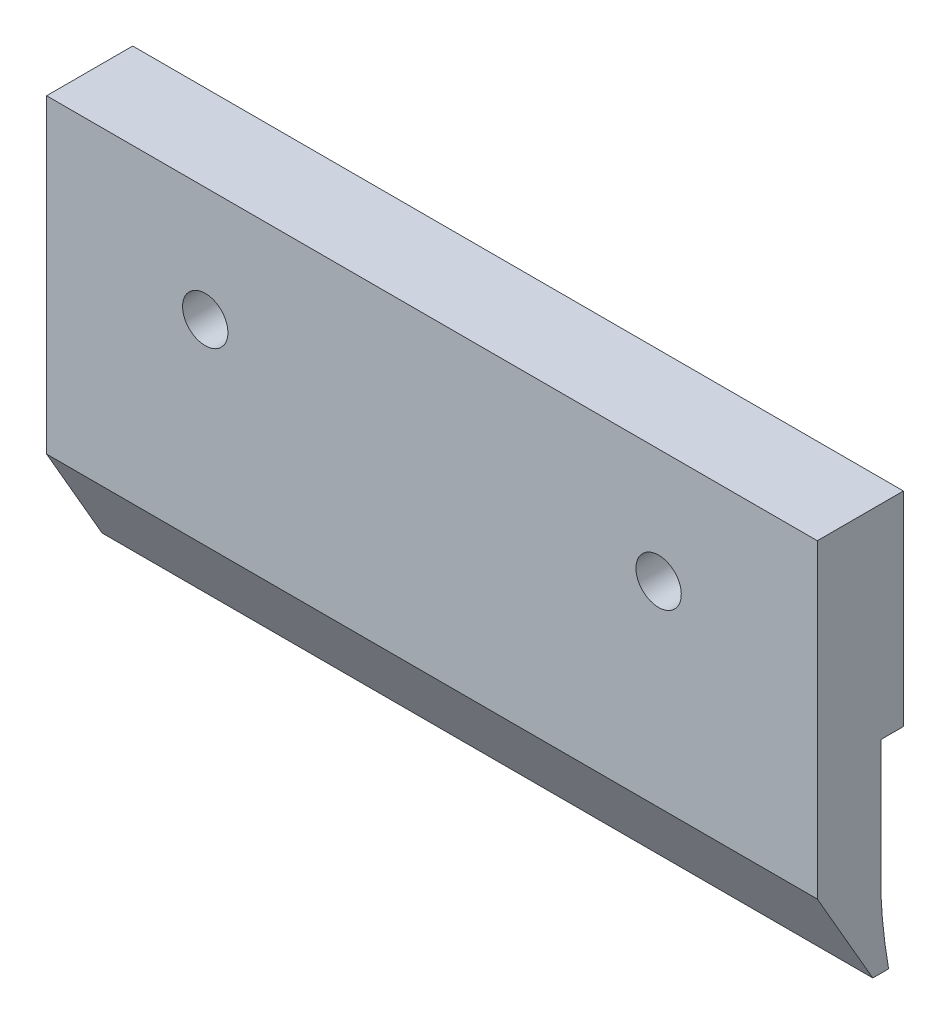
SolidWorks part; units mm, degrees
ref_plane "Front Plane" through (0, 0, 0) normal (0, 0, 1) x (1, 0, 0)
ref_plane "Top Plane" through (0, 0, 0) normal (0, 1, 0) x (1, 0, 0)
ref_plane "Right Plane" through (0, 0, 0) normal (1, 0, 0) x (0, 0, -1)
sketch "Sketch1" plane through (0, 0, 0) normal (1, 0, 0) x (0, 0, -1)
  line L0 (0, 0) -> (1, 0)
  line L1 (1, 0) -> (1, 9)
  line L2 (0, 0) -> (0, -5.7849)
  line L3 (0, 0) -> (0, -5.7849) construction
  line L4 (1, 9) -> (-2.8, 9)
  line L5 (-2.8, 9) -> (-2.8, 0)
  line L6 (-2.8, 0) -> (-2.8, -4.6892)
  line L10 (-0.3512, -8.9306) -> (-2.8, -4.6892)
  line L11 (-0.3512, -8.9306) -> (0, -8.9306)
  line L13 (0, -8.9306) -> (0.3465, -8.9306)
  spline S0 degree 2 poles (0, -5.7849) (0.0681, -7.3693) (0.3465, -8.9306) knots 0 0 0 1 1 1
  dimension "D1" = 9
  dimension "D3" = 1
  dimension "D4" = 2.8
  dimension "D5" = 8.9306
  dimension "D7" = 4.2415
  dimension "D9" = 4.6892
  dimension "D10" = 0.3512
sketch "Sketch2" plane through (0, 0, 0) normal (0, 0, 1) x (1, 0, 0)
  line L0 (-17.2885, 9) -> (17.2885, 9)
  line L3 (17.2885, -4.5545) -> (17.2885, -7.0545)
  line L6 (0, 9) -> (0, -8.0545) construction
  line L7 (-16.2885, -8.0545) -> (16.2885, -8.0545)
  line L8 (17.2885, 9) -> (17.2885, 0)
  line L9 (17.2885, 0) -> (17.2885, -4.5545)
  line L10 (-17.2885, 0) -> (-17.2885, -4.5545)
  line L11 (-17.2885, 9) -> (-17.2885, 0)
  line L12 (-17.2885, -4.5545) -> (-17.2885, -7.0545)
  arc A0 (16.2885, -8.0545) -> (17.2885, -7.0545) centre (16.2885, -7.0545) ccw
  arc A1 (-16.2885, -8.0545) -> (-17.2885, -7.0545) centre (-16.2885, -7.0545) cw
  point P2 (0, 0)
  point P6 (0, 0)
  point P7 (0, 0)
  point P8 (0, 0)
  point P13 (0, 0)
  point P14 (0, 0)
  point P17 (17.2885, -8.0545)
  dimension "D5" = 1
  dimension "D1" = 17.2885
  dimension "D2" = 9
  dimension "D3" = 8.0545
  dimension "D4" = 3.5
extrude "Boss-Extrude1" add sketch "Sketch1" along normal blind 17 and the other way blind 17
sketch "Sketch4" plane through (0, 0, -1) normal (0, 0, -1) x (-1, 0, 0)
  line L0 (0, 0) -> (0, 3.95)
  line L1 (0, 9) -> (0, -8.0545) construction
  line L2 (0, 3.95) -> (-10, 3.95)
  circle A0 centre (-10, 3.95) radius 1
  circle A1 centre (10, 3.95) radius 1
  dimension "D1" = 10
  dimension "D2" = 3.95
extrude "Cut-Extrude1" cut sketch "Sketch4" against normal blind 17 contours A0 | A1 region at (10.9717, 3.95, -1) region at (-10, 3.95, -1)
